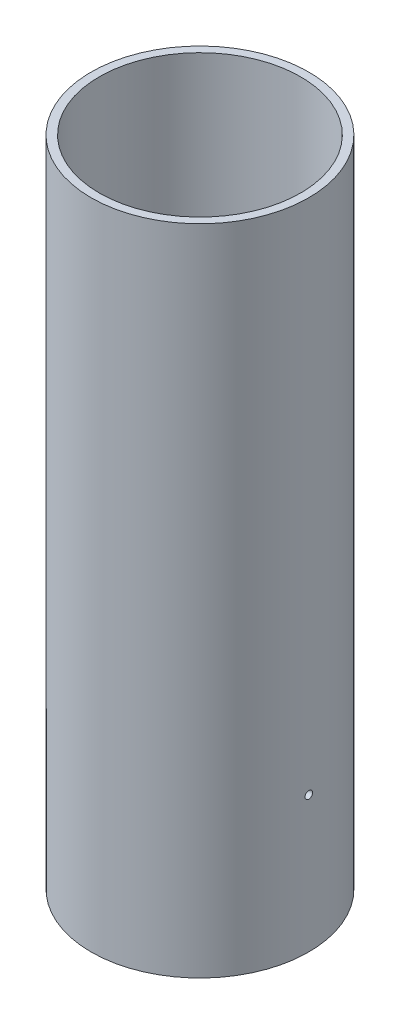
SolidWorks part; units mm, degrees
material "Glass"
ref_plane "Front Plane" through (0, 0, 0) normal (0, 0, 1) x (1, 0, 0)
ref_plane "Top Plane" through (0, 0, 0) normal (0, 1, 0) x (1, 0, 0)
ref_plane "Right Plane" through (0, 0, 0) normal (1, 0, 0) x (0, 0, -1)
sketch "Sketch1" plane through (0, 0, 0) normal (0, 1, 0) x (1, 0, 0)
  circle A0 centre (0, 0) radius 50.8
  circle A1 centre (0, 0) radius 46.99
  dimension "D1" = 101.6
  dimension "D2" = 93.98
extrude "Boss-Extrude1" add sketch "Sketch1" along normal blind 304.8
ref_plane "Plane1" through (50.8, 0, 0) normal (1, 0, 0) x (0, 0, -1)
sketch "Sketch2" plane through (50.8, 0, 0) normal (1, 0, 0) x (0, 0, -1)
  line L0 (-46.99, 0) -> (46.99, 0) construction
  circle A0 centre (0, 63.5) radius 1.7526
  dimension "D2" = 3.5052
  dimension "D1" = 63.5
extrude "Cut-Extrude1" cut sketch "Sketch2" against normal up to next
pattern_circular "CirPattern1" count 2 over 360 about axis through (0, 0, 0) along (0, 1, 0) of "Cut-Extrude1"
